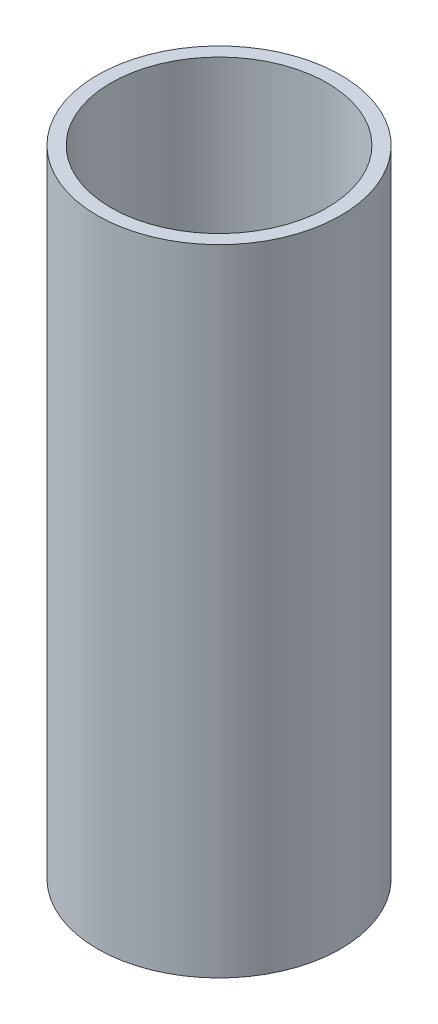
SolidWorks part; units mm, degrees
ref_plane "Front Plane" through (0, 0, 0) normal (0, 0, 1) x (1, 0, 0)
ref_plane "Top Plane" through (0, 0, 0) normal (0, 1, 0) x (1, 0, 0)
ref_plane "Right Plane" through (0, 0, 0) normal (1, 0, 0) x (0, 0, -1)
sketch "Sketch1" plane through (0, 0, 0) normal (0, 1, 0) x (1, 0, 0)
  circle A0 centre (0, 0) radius 42.5
  dimension "SLEEVE_OD" = 85
extrude "Boss-Extrude1" add sketch "Sketch1" along normal blind 221.7958
sketch "Sketch2" plane through (0, 0, 0) normal (0, 1, 0) x (1, 0, 0)
  circle A0 centre (0, 0) radius 37.7575
  dimension "BORE_D" = 75.5151
extrude "Cut-Extrude1" cut sketch "Sketch2" along normal through all
chamfer "Chamfer1" distance 2.733 angle 60 rebuild error yes
